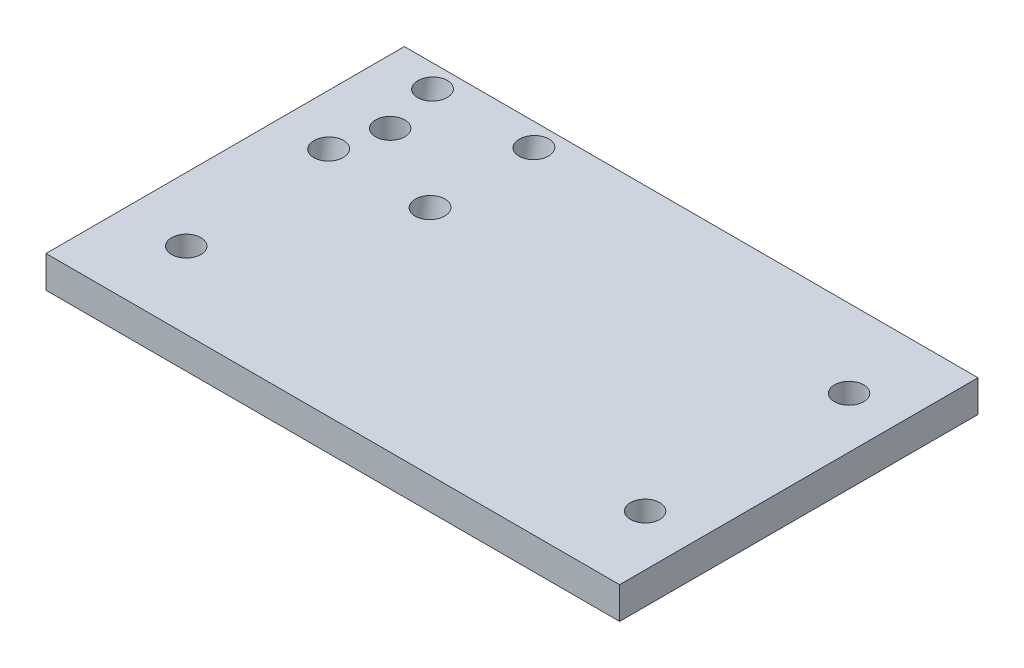
SolidWorks part; units mm, degrees
ref_plane "Front" through (0, 0, 0) normal (0, 0, 1) x (1, 0, 0)
ref_plane "Top" through (0, 0, 0) normal (0, 1, 0) x (1, 0, 0)
ref_plane "Right" through (0, 0, 0) normal (1, 0, 0) x (0, 0, -1)
sketch "Sketch1" plane through (0, 0, 0) normal (0, 1, 0) x (1, 0, 0)
  line L1 (0, 0) -> (90, 0)
  line L2 (0, 0) -> (0, 56.23)
  line L3 (0, 56.23) -> (90, 56.23)
  line L4 (90, 0) -> (90, 56.23)
  dimension "D1" = 90
  dimension "D2" = 56.23
extrude "Boss-Extrude1" add sketch "Sketch1" along normal blind 5
sketch "Sketch2" plane through (0, 5, 0) normal (0, 1, 0) x (1, 0, 0)
  circle A0 centre (82, 12) radius 2.3
  circle A1 centre (10, 12) radius 2.3
extrude "Cut-Extrude1" cut sketch "Sketch2" against normal blind 15
sketch "Sketch4" plane through (0, 5, 0) normal (0, 1, 0) x (1, 0, 0)
  circle A0 centre (39.2121, 27.5705) radius 2.204
  circle A1 centre (23.8176, 32.2728) radius 4.0674
  circle A2 centre (43.572, 44.174) radius 17.6111
  circle A3 centre (28.1775, 48.8763) radius 2.2
ref_plane "Plane1" through (0, 15.35, -2.9837) normal (0, 0.9816, -0.1908) x (-1, 0, 0)
sketch "Sketch7" plane through (0, 5, 0) normal (0, 1, 0) x (1, 0, 0)
  circle A0 centre (82, 44) radius 2.3
  circle A1 centre (10, 44) radius 2.3
extrude "Cut-Extrude3" cut sketch "Sketch7" against normal blind 45
sketch "Sketch9" plane through (0, 5, 0) normal (0, 1, 0) x (1, 0, 0)
  circle A0 centre (23.822, 36.623) radius 2.3
  circle A1 centre (7.898, 36.623) radius 2.3
  circle A2 centre (23.822, 52.8913) radius 2.3
  circle A3 centre (7.898, 52.8913) radius 2.3
sketch "Sketch10" plane through (0, 15.35, -2.9837) normal (0, 0.9816, -0.1908) x (-1, 0, 0)
  line L0 (-90, -54.2429) -> (0, -54.2429) construction
  circle A0 centre (-7.9803, -50.7429) radius 2.3
  circle A1 centre (-23.8905, -50.7429) radius 2.3
  circle A2 centre (-7.9803, -34.7429) radius 2.3
  circle A3 centre (-23.8905, -34.7429) radius 2.3
  dimension "D1" = 16
  dimension "D2" = 16
  dimension "D3" = 3.5
  dimension "D4" = 3.5
extrude "Cut-Extrude4" cut sketch "Sketch10" against normal blind 10
